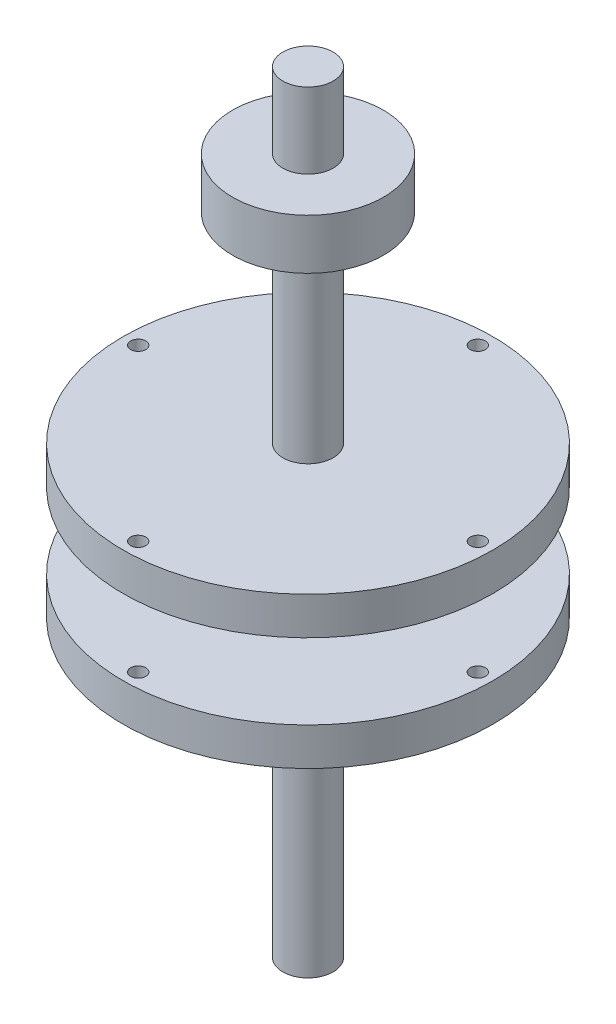
SolidWorks part; units mm, degrees
ref_plane "Front Plane" through (0, 0, 0) normal (0, 0, 1) x (1, 0, 0)
ref_plane "Top Plane" through (0, 0, 0) normal (0, 1, 0) x (1, 0, 0)
ref_plane "Right Plane" through (0, 0, 0) normal (1, 0, 0) x (0, 0, -1)
sketch "Sketch1" plane through (0, 0, 0) normal (0, 0, 1) x (1, 0, 0)
  line L0 (0, 223.9568) -> (0, -251.1973) construction
  line L1 (-10, -153.3547) -> (10, -153.3547)
  line L2 (-10, -153.3547) -> (-10, 153.3548)
  line L3 (-10, 153.3548) -> (10, 153.3548)
  line L4 (10, -153.3547) -> (10, -36.3547)
  line L5 (-10, -153.3547) -> (10, 153.3548) construction
  line L6 (-10, 153.3548) -> (10, -153.3547) construction
  line L7 (-30, 123.3548) -> (30, 123.3548)
  line L8 (-30, 123.3548) -> (-30, 103.3548)
  line L9 (-30, 103.3548) -> (30, 103.3548)
  line L10 (30, 123.3548) -> (30, 103.3548)
  line L11 (-30, 123.3548) -> (30, 103.3548) construction
  line L12 (-30, 103.3548) -> (30, 123.3548) construction
  line L13 (10, -21.3547) -> (10, 8.6453)
  line L17 (73.5, 23.6453) -> (73.5, 8.6453)
  line L18 (0, 153.3548) -> (0, -153.3547)
  line L20 (73.5, 8.6453) -> (10, 8.6453)
  line L22 (73.5, -21.3547) -> (10, -21.3547)
  line L23 (10, 8.6453) -> (10, -21.3547)
  line L24 (73.5, -21.3547) -> (73.5, -36.3547)
  line L25 (10, 23.6453) -> (10, 153.3548)
  line L26 (10, 23.6453) -> (73.5, 23.6453)
  line L27 (10, -36.3547) -> (73.5, -36.3547)
  point P0 (0, 0)
  point P6 (0, 113.3548)
  dimension "D1" = 20
  dimension "D2" = 20
  dimension "D3" = 60
  dimension "D4" = 50
  dimension "D5" = 256.7095
  dimension "D7" = 60
  dimension "D8" = 73.5
  dimension "D10" = 30
  dimension "D9" = 15
  dimension "D6" = 79.7095
revolve "Revolve3" add sketch "Sketch1" angle 360 about L0 region at (2.6702, -25, 0) region at (5, 113.3548, 0) region at (20, 113.3548, 0) region at (5, 138.3548, 0)
sketch "Sketch2" plane through (0, -36.3547, 0) normal (0, -1, 0) x (1, 0, 0)
  line L1 (-67.5, 67.5) -> (67.5, 67.5) construction
  line L2 (-67.5, 67.5) -> (-67.5, -67.5) construction
  line L3 (-67.5, -67.5) -> (67.5, -67.5) construction
  line L4 (67.5, 67.5) -> (67.5, -67.5) construction
  line L5 (-67.5, 67.5) -> (67.5, -67.5) construction
  line L6 (-67.5, -67.5) -> (67.5, 67.5) construction
  circle A0 centre (67.5, 0) radius 3
  circle A1 centre (-67.5, 0) radius 3
  circle A2 centre (0, 67.5) radius 3
  circle A3 centre (0, -67.5) radius 3
  point P0 (0, 0)
  dimension "D2" = 6
  dimension "D1" = 135
extrude "Cut-Extrude1" cut sketch "Sketch2" against normal blind 80
equation "\"hatchHoleDiameter\"=600mm"
equation "\"hullThickness\"=177.1mm"
equation "\"gasketHullInterconnectWidth\"=100mm"
equation "\"collarThickness\"=20mm"
equation "\"hatchTunnelLength\"=200mm"
equation "\"oRingDiameter\"=2mm"
equation "\"boltPatternRadiusInterconnect\"=500mm"
equation "\"interconnectBoltDiameter\"=30mm"
equation "\"hatchShaftDiameter\"=20mm"
equation "\"hatchMinima\"=39.9mm"
equation "\"hullDiameter\"=2240mm"
equation "\"hatchMaxima\"=180mm"
equation "\"bushingFlatHatch\"=15mm"
equation "\"hingePivotDiameter\"=20mm"
equation "\"handleWidth\"=250mm"
equation "\"handleHeight\"=160mm"
equation "\"handleThickness\"=25mm"
equation "\"FrameLength\"=2600mm"
equation "\"FrameMidLength\"=1800mm"
equation "\"TubeOD\"=100mm"
equation "\"FrameBackFlat\"=500mm"
equation "\"TubeWall\"=15.0001mm"
equation "\"TopMemberAngle\"=140deg"
equation "\"D1@Sketch1\"=\"hatchShaftDiameter\""
equation "\"HatchShaftSeatThickness\"=20mm"
equation "\"D2@Sketch1\"=\"HatchShaftSeatThickness\""
equation "\"D3@Sketch1\"=\"hatchShaftDiameter\"*3"
equation "\"D5@Sketch1\"=\"hatchEdgeToTop\"+\"hatchMaxima\""
equation "\"hatchTopToDogArmCenter\"=33mm"
equation "\"dogArmSize\"=30mm"
equation "\"hatchPivotHeight\"=40mm"
equation "\"hatchPivotDistance\"=70mm"
equation "\"HatchORingDiameter\"=2.1mm"
equation "\"hatchThickness\"=39.9mm"
equation "\"hatchEdgeToTop\"=76.7095mm"
equation "\"D7@Sketch1\"=\"dogArmSize\"*2"
equation "\"D9@Sketch1\"=\"dogArmSize\"/2"
equation "\"D6@Sketch1\"=\"hatchTopToDogArmCenter\"+\"hatchEdgeToTop\"-\"dogArmSize\""
equation "\"D1@Sketch2\"=67.5*2"
